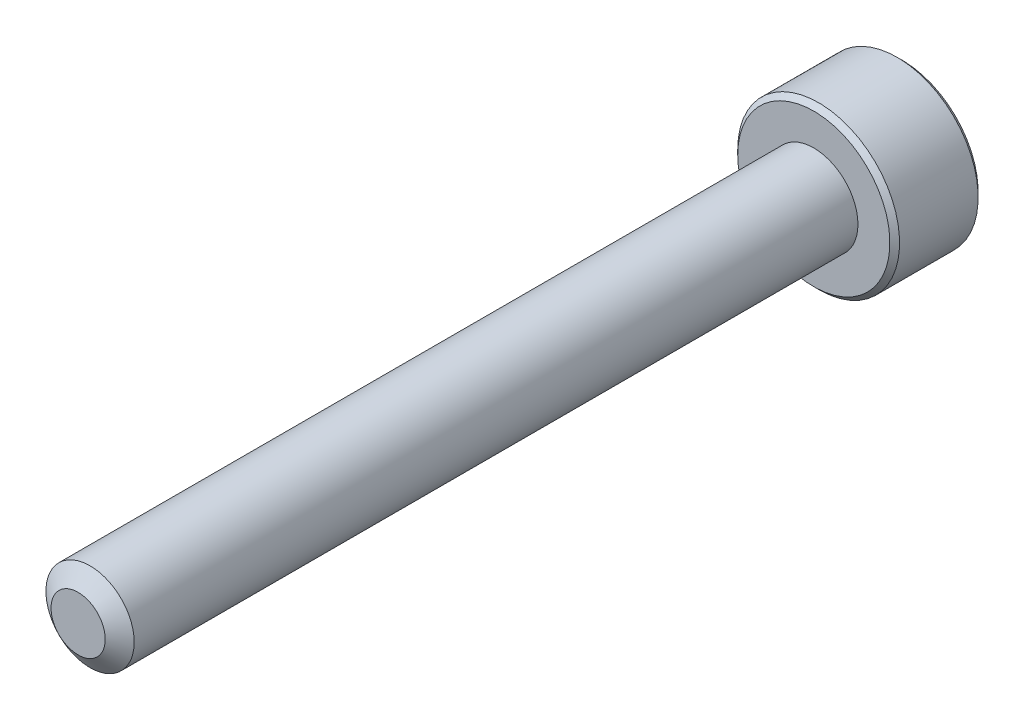
SolidWorks part; units mm, degrees
ref_plane "Front Plane" through (0, 0, 0) normal (0, 0, 1) x (1, 0, 0)
ref_plane "Top Plane" through (0, 0, 0) normal (0, 1, 0) x (1, 0, 0)
ref_plane "Right Plane" through (0, 0, 0) normal (1, 0, 0) x (0, 0, -1)
sketch "Sketch1" plane through (0, 0, 0) normal (0, 0, 1) x (1, 0, 0)
  circle A0 centre (0, 0) radius 1.5
  dimension "OD" = 3
extrude "Extrude1" add sketch "Sketch1" against normal blind 25
sketch "Sketch2" plane through (0, 0, 0) normal (0, 0, 1) x (1, 0, 0)
  circle A0 centre (0, 0) radius 1.5 construction
  circle A1 centre (0, 0) radius 1.5
curve "Helix/Spiral1" pitch 0.5 height 25.5 turns 51 parameters "pitch"=0.5
sketch "Sketch3" plane through (0, 0, 0) normal (1, 0, 0) x (0, 0, -1)
  line L0 (-0.4375, 1.5) -> (-0.25, 1.1752)
  line L1 (-0.25, 1.1752) -> (-0.1875, 1.1752)
  line L2 (-0.1875, 1.1752) -> (0, 1.5)
  line L3 (-0.4375, 1.5) -> (0, 1.5)
  line L4 (-0.2187, 1.5) -> (-0.2187, 1.1752) construction
  line L5 (-0.3437, 1.3376) -> (-0.0937, 1.3376) construction
  line L6 (0, 1.5) -> (0, -1.5) construction
  line L7 (0, -1.5) -> (25, -1.5) construction
  point P11 (2.25, -1.5)
  dimension "D1" = 0.0625
  dimension "D2" = 0.25
  dimension "D3" = 60
  dimension "D4" = 2.25
sweep "Cut-Sweep1" [suppressed] cut profiles "Sketch3" path "Helix/Spiral1"
sketch "Sketch4" plane through (0, 0, 0) normal (1, 0, 0) x (0, 0, -1)
  line L0 (0.4053, 1.5) -> (0, 0.9212)
  line L1 (0, 0.9212) -> (0, 1.5)
  line L2 (0.4053, 1.5) -> (0, 1.5)
  line L3 (-0.4375, 1.5) -> (0, 1.5) construction
  line L4 (0, 0) -> (7.0209, 0) construction
  dimension "D1" = 55
  dimension "D2" = 0.254
revolve "Cut-Revolve1" cut sketch "Sketch4" angle 360 about L4
sketch "Sketch5" [suppressed] plane through (0, 0, 0) normal (1, 0, 0) x (0, 0, -1)
  line L0 (25, -1.1822) -> (25, 1.0703) construction
  line L1 (25, 1.5) -> (18.1202, 1.5)
  line L2 (25, 1.5) -> (25, 0)
  line L3 (25, 0) -> (18, 0)
  line L4 (18, 1.1698) -> (18, 0)
  line L5 (18.1202, 1.5) -> (18, 1.1698)
  line L6 (0, 0) -> (9.9695, 0) construction
  point P3 (18, 1.5)
  point P10 (18, 1.5)
  dimension "D1" = 0.3302
  dimension "D3" = 20
  dimension "Thread Min" = 18
revolve "partially thread" [suppressed] add sketch "Sketch5" angle 360 about L6
sketch "Sketch6" plane through (0, 0, -25) normal (0, 0, -1) x (-1, 0, 0)
  circle A0 centre (0, 0) radius 2.75
  dimension "head dia" = 5.5
extrude "Extrude2" add sketch "Sketch6" along normal blind 3
sketch "Sketch7" plane through (0, 0, -28) normal (0, 0, -1) x (-1, 0, 0)
  line L1 (0, 1.4434) -> (-1.25, 0.7217)
  line L2 (-1.25, 0.7217) -> (-1.25, -0.7217)
  line L3 (-1.25, -0.7217) -> (0, -1.4434)
  line L4 (0, -1.4434) -> (1.25, -0.7217)
  line L5 (1.25, -0.7217) -> (1.25, 0.7217)
  line L6 (1.25, 0.7217) -> (0, 1.4434)
  circle A0 centre (0, 0) radius 1.25 construction
  dimension "hex dia" = 2.5
extrude "Cut-Extrude1" cut sketch "Sketch7" against normal blind 1.875
sketch "Sketch8" plane through (0, 0, -28) normal (0, 0, -1) x (-1, 0, 0)
  circle A0 centre (0, 0) radius 1.4434
extrude "Cut-Extrude2" cut sketch "Sketch8" against normal through all draft 45
chamfer "Chamfer1" distance 0.165 angle 45 2 edges at (-2.75, 0, -28) (-2.75, 0, -25)
sketch "Sketch9" plane through (0, 0, 0) normal (1, 0, 0) x (0, 0, -1)
  line L0 (0, 1.5) -> (0, -1.5) construction
  line L1 (2.75, 1.5) -> (2.75, -1.5) construction
  dimension "D1" = 2.75
sketch "Sketch10" plane through (0, 0, 0) normal (1, 0, 0) x (0, 0, -1)
  line L0 (25, 1.5) -> (25, 0)
  line L1 (25, 1.5) -> (24.875, 1.5)
  line L2 (24.875, 1.5) -> (24.2537, 0)
  line L3 (25, 0) -> (24.2537, 0)
  line L4 (25, 2.585) -> (25, -2.585) construction
  dimension "D1" = 22.5
  dimension "D2" = 0.125
revolve "Revolve1" [suppressed] add sketch "Sketch10" angle 360 about L3
equation "\"D3@Helix/Spiral1\" = \"screw length@Extrude1\"+\"pitch@Helix/Spiral1\""
equation "\"D1@Sketch3\" = \"pitch@Helix/Spiral1\"*.125"
equation "\"D2@Sketch3\" = \"pitch@Helix/Spiral1\"*.5"
equation "\"D1@Cut-Extrude1\" = \"hex dia@Sketch7\"*.75"
equation "\"D1@Chamfer1\" = \"head dia@Sketch6\"*.03"
equation "\"D1@Sketch9\" = \"pitch@Helix/Spiral1\"*5.5"
equation "\"D2@Sketch10\" = \"pitch@Helix/Spiral1\"*.25"
equation "\"D4@Sketch3\" = \"pitch@Helix/Spiral1\"*4.50"
